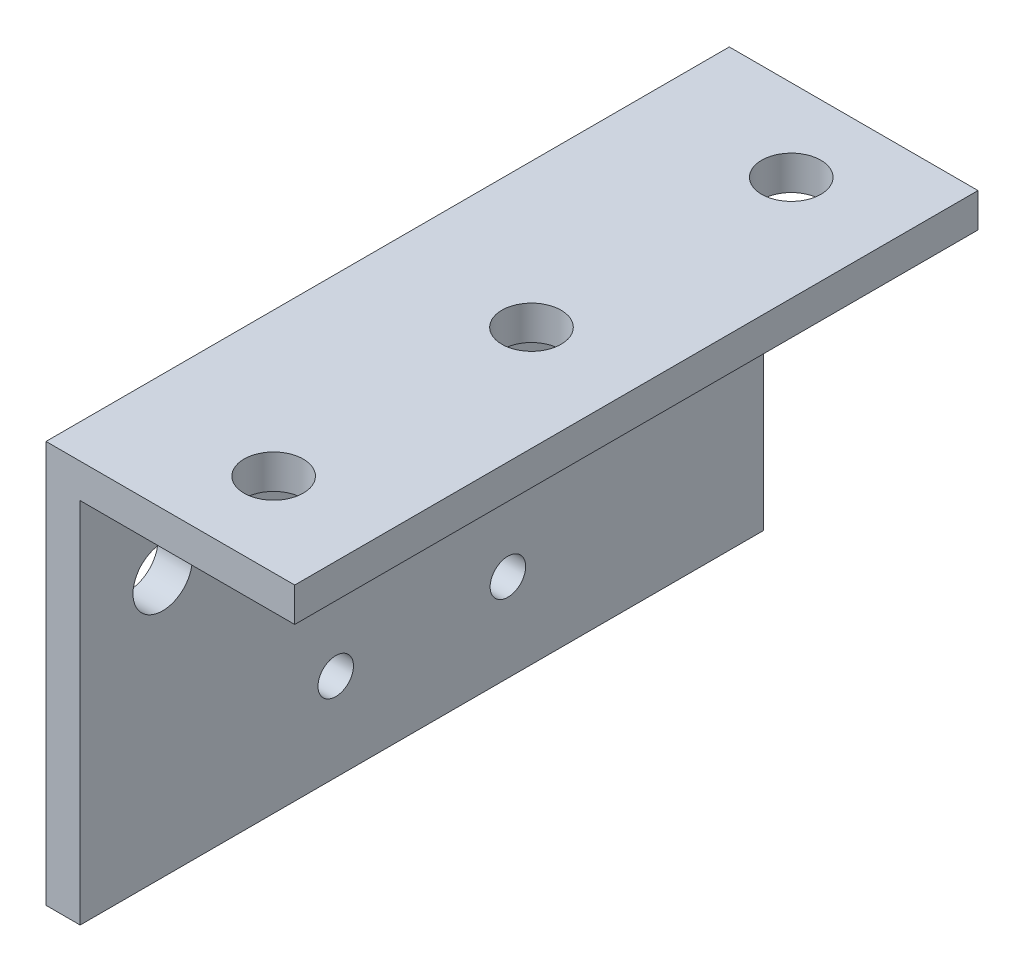
SolidWorks part; units mm, degrees
material "6061 Alloy"
ref_plane "Front Plane" through (0, 0, 0) normal (0, 0, 1) x (1, 0, 0)
ref_plane "Top Plane" through (0, 0, 0) normal (0, 1, 0) x (1, 0, 0)
ref_plane "Right Plane" through (0, 0, 0) normal (1, 0, 0) x (0, 0, -1)
sketch "Sketch1" plane through (0, 0, 0) normal (0, 0, 1) x (1, 0, 0)
  line L0 (0, 0) -> (0, 37.338)
  line L1 (0, 37.338) -> (23.114, 37.338)
  line L2 (23.114, 37.338) -> (23.114, 34.163)
  line L3 (0, 0) -> (3.175, 0)
  line L4 (3.175, 0) -> (3.175, 34.163)
  line L5 (3.175, 34.163) -> (23.114, 34.163)
  dimension "D1" = 37.338
  dimension "D2" = 23.114
  dimension "D3" = 3.175
  dimension "D4" = 3.175
extrude "Boss-Extrude1" add sketch "Sketch1" along normal blind 63.5
sketch "Sketch21" plane through (0, 0, 0) normal (-1, 0, 0) x (0, 0, 1)
  line L0 (31.75, 0) -> (31.75, 37.338) construction
  line L1 (63.5, 0) -> (0, 0) construction
  line L2 (63.5, 37.338) -> (0, 37.338) construction
  point P3 (31.75, 18.669)
sketch "Sketch28" plane through (0, 37.338, 0) normal (0, 1, 0) x (1, 0, 0)
  line L0 (23.114, -31.75) -> (0, -31.75) construction
  line L2 (23.114, -63.5) -> (23.114, 0) construction
  point P3 (11.557, -31.75)
sketch "Sketch29" plane through (0, 0, 0) normal (-1, 0, 0) x (0, 0, 1)
  line L0 (0, 24.2082) -> (63.5, 24.2082) construction
  line L1 (0, 37.338) -> (0, 0) construction
  line L2 (63.5, 37.338) -> (63.5, 0) construction
sketch "Sketch30" plane through (0, 37.338, 0) normal (0, 1, 0) x (1, 0, 0)
  line L0 (13.3686, 0) -> (13.3686, -63.5) construction
  line L1 (23.114, 0) -> (0, 0) construction
  line L2 (23.114, -63.5) -> (0, -63.5) construction
sketch "Sketch31" plane through (0, 0, 0) normal (-1, 0, 0) x (0, 0, 1)
  line L0 (31.75, 24.2082) -> (10.16, 24.2082) construction
  line L1 (0, 24.2082) -> (63.5, 24.2082) construction
  line L2 (31.75, 24.2082) -> (53.34, 24.2082) construction
sketch "Sketch32" plane through (0, 37.338, 0) normal (0, 1, 0) x (1, 0, 0)
  line L0 (13.3686, -31.75) -> (13.3686, -53.34) construction
  line L1 (13.3686, 0) -> (13.3686, -63.5) construction
  line L2 (13.3686, -31.75) -> (13.3686, -10.16) construction
hole_wizard "M5 Clearance Hole1" positions "Sketch35" profile "Sketch36" hole size "M5" standard "ANSI Metric" end condition through all
sketch "Sketch35" plane through (0, 0, 0) normal (-1, 0, 0) x (0, 0, 1)
  line L0 (0, 24.2082) -> (63.5, 24.2082) construction
  point P0 (55.8413, 24.2082)
sketch "Sketch36" plane through (0, 24.2082, 55.8413) normal (0, 1, 0) x (0, 0, 1)
  line L0 (0, 0) -> (0, 23.114)
  line L1 (0, 23.114) -> (2.75, 23.114)
  line L2 (2.75, 23.114) -> (2.75, 0)
  line L5 (2.75, 0) -> (0, 0)
  line L11 (0, -6.35) -> (0, 107.95) construction
  dimension "Thru Hole Dia." = 5.5
  dimension "Thru Hole Depth" = 23.114
hole_wizard "M5 Clearance Hole2" positions "Sketch37" profile "Sketch38" hole size "M5" standard "ANSI Metric" end condition through all
sketch "Sketch37" plane through (0, 0, 0) normal (-1, 0, 0) x (0, 0, 1)
  line L0 (0, 24.2082) -> (63.5, 24.2082) construction
  point P0 (7.6776, 24.2082)
sketch "Sketch38" plane through (0, 24.2082, 7.6776) normal (0, 1, 0) x (0, 0, 1)
  line L0 (0, 0) -> (0, 23.114)
  line L1 (0, 23.114) -> (2.75, 23.114)
  line L2 (2.75, 23.114) -> (2.75, 0)
  line L5 (2.75, 0) -> (0, 0)
  line L11 (0, -6.35) -> (0, 107.95) construction
  dimension "Thru Hole Dia." = 5.5
  dimension "Thru Hole Depth" = 23.114
hole_wizard "M5 Clearance Hole3" positions "Sketch39" profile "Sketch40" hole size "M5" standard "ANSI Metric" end condition through all
sketch "Sketch39" plane through (0, 37.338, 0) normal (0, 1, 0) x (1, 0, 0)
  point P0 (13.3686, -31.75)
sketch "Sketch40" plane through (13.3686, 37.338, 31.75) normal (1, 0, 0) x (0, 0, 1)
  line L0 (0, 0) -> (0, 37.338)
  line L1 (0, 37.338) -> (2.75, 37.338)
  line L2 (2.75, 37.338) -> (2.75, 0)
  line L5 (2.75, 0) -> (0, 0)
  line L11 (0, -6.35) -> (0, 107.95) construction
  dimension "Thru Hole Dia." = 5.5
  dimension "Thru Hole Depth" = 37.338
hole_wizard "M5 Clearance Hole4" positions "Sketch43" profile "Sketch44" hole size "M5" standard "ANSI Metric" end condition through all
sketch "Sketch43" plane through (0, 37.338, 0) normal (0, 1, 0) x (1, 0, 0)
  line L0 (13.3686, 0) -> (13.3686, -63.5) construction
  point P0 (13.3686, -55.7137)
sketch "Sketch44" plane through (13.3686, 37.338, 55.7137) normal (1, 0, 0) x (0, 0, 1)
  line L0 (0, 0) -> (0, 37.338)
  line L1 (0, 37.338) -> (2.75, 37.338)
  line L2 (2.75, 37.338) -> (2.75, 0)
  line L5 (2.75, 0) -> (0, 0)
  line L11 (0, -6.35) -> (0, 107.95) construction
  dimension "Thru Hole Dia." = 5.5
  dimension "Thru Hole Depth" = 37.338
hole_wizard "M5 Clearance Hole5" positions "Sketch49" profile "Sketch50" hole size "M5" standard "ANSI Metric" end condition through all
sketch "Sketch49" plane through (0, 37.338, 0) normal (0, 1, 0) x (1, 0, 0)
  line L0 (13.3686, 0) -> (13.3686, -63.5) construction
  point P0 (13.3686, -7.6106)
sketch "Sketch50" plane through (13.3686, 37.338, 7.6106) normal (1, 0, 0) x (0, 0, 1)
  line L0 (0, 0) -> (0, 37.338)
  line L1 (0, 37.338) -> (2.75, 37.338)
  line L2 (2.75, 37.338) -> (2.75, 0)
  line L5 (2.75, 0) -> (0, 0)
  line L11 (0, -6.35) -> (0, 107.95) construction
  dimension "Thru Hole Dia." = 5.5
  dimension "Thru Hole Depth" = 37.338
sketch "Sketch51" plane through (0, 0, 0) normal (-1, 0, 0) x (0, 0, 1)
  line L0 (63.5, 34.163) -> (0, 34.163) construction
  line L1 (39.75, 24.163) -> (23.75, 24.163) construction
  line L2 (39.75, 24.163) -> (39.75, 8.163) construction
  line L3 (39.75, 8.163) -> (23.75, 8.163) construction
  line L4 (23.75, 24.163) -> (23.75, 8.163) construction
  line L5 (39.75, 24.163) -> (23.75, 8.163) construction
  line L6 (39.75, 8.163) -> (23.75, 24.163) construction
  line L7 (31.75, 37.338) -> (31.75, 0) construction
  line L8 (63.5, 37.338) -> (0, 37.338) construction
  line L9 (63.5, 0) -> (0, 0) construction
  circle A0 centre (31.75, 16.163) radius 5 construction
  point P0 (31.75, 16.163)
  dimension "D4" = 10
  dimension "D1" = 10
  dimension "D2" = 16
  dimension "D3" = 16
hole_wizard "Tap Drill for M4x0.7 Tap2" positions "Sketch52" profile "Sketch53" hole size "M4x0.7" standard "ANSI Metric" end condition through all
sketch "Sketch52" plane through (0, 0, 0) normal (-1, 0, 0) x (0, 0, 1)
  point P0 (23.75, 24.163)
  point P3 (23.75, 8.163)
  point P6 (39.75, 8.163)
  point P9 (39.75, 24.163)
sketch "Sketch53" plane through (0, 24.163, 23.75) normal (0, 1, 0) x (0, 0, 1)
  line L0 (0, 0) -> (0, 23.114)
  line L1 (0, 23.114) -> (1.65, 23.114)
  line L2 (1.65, 23.114) -> (1.65, 0)
  line L5 (1.65, 0) -> (0, 0)
  line L11 (0, -6.35) -> (0, 107.95) construction
  dimension "Thru Hole Dia." = 3.3
  dimension "Thru Hole Depth" = 23.114
